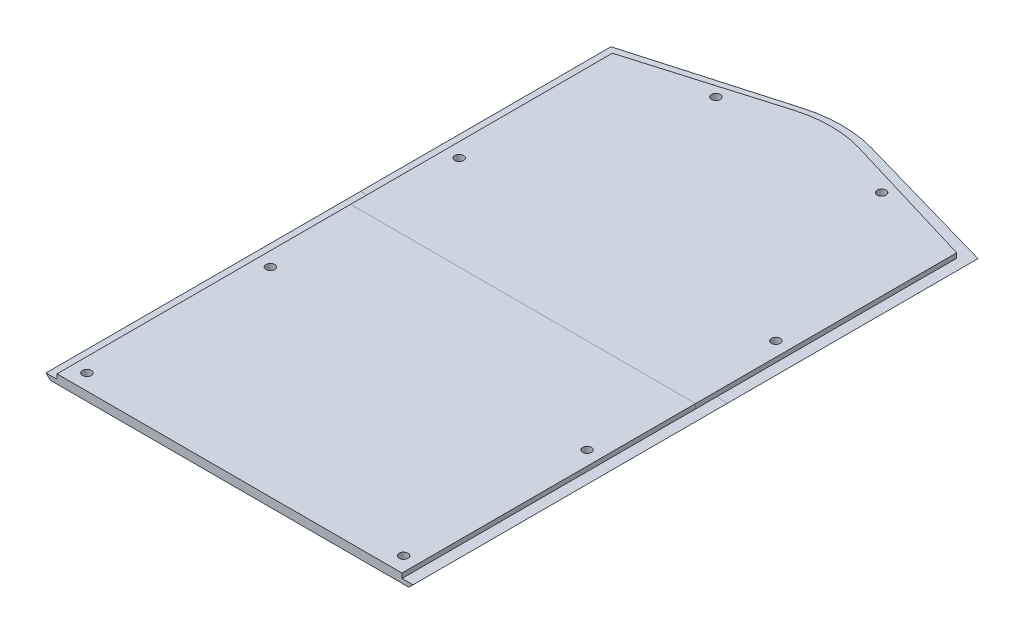
SolidWorks part; units mm, degrees
ref_plane "Front Plane" through (0, 0, 0) normal (0, 0, 1) x (1, 0, 0)
ref_plane "Top Plane" through (0, 0, 0) normal (0, 1, 0) x (1, 0, 0)
ref_plane "Right Plane" through (0, 0, 0) normal (1, 0, 0) x (0, 0, -1)
sketch "Sketch3" plane through (0, 0, 0) normal (0, -1, 0) x (1, 0, 0)
  line L0 (-82.5, -125) -> (-82.5, 140) construction
  line L1 (-15.1576, -144.8692) -> (-82.5, -125) construction
  line L2 (82.5923, -125) -> (15.2499, -144.8692) construction
  line L3 (82.5, 140) -> (82.5, -125) construction
  line L4 (-82.5, -125) -> (-82.5, 140) construction
  line L5 (-15.1576, -144.8692) -> (-82.5, -125) construction
  line L6 (82.5923, -125) -> (15.2499, -144.8692) construction
  line L7 (82.5, 140) -> (82.5, -125) construction
  line L8 (82.25, 140) -> (82.25, -124.5028)
  line L9 (82.5923, -125) -> (82.5, -125) construction
  line L10 (-15.0878, -144.6291) -> (-82.25, -124.8131)
  line L11 (-82.25, -124.8131) -> (-82.25, 140)
  line L12 (82.25, -124.5028) -> (15.1801, -144.6291)
  line L13 (82.25, 140) -> (-82.25, 140)
  line L14 (82.5216, -124.7602) -> (15.1801, -144.6291) construction
  line L15 (82.25, 140) -> (82.25, -125) construction
  arc A0 (-15.1576, -144.8692) -> (0.0462, -146.9988) centre (-0.0004, -91.995) ccw construction
  arc A1 (0.0462, -146.9988) -> (15.2499, -144.8692) centre (0.0928, -91.995) ccw construction
  arc A2 (-15.1576, -144.8692) -> (0.0462, -146.9988) centre (-0.0004, -91.995) ccw construction
  arc A3 (0.0462, -146.9988) -> (15.2499, -144.8692) centre (0.0928, -91.995) ccw construction
  arc A4 (0.0462, -146.7488) -> (15.1801, -144.6291) centre (0.0928, -91.995) ccw
  arc A5 (-15.0878, -144.6291) -> (0.0462, -146.7488) centre (-0.0004, -91.995) ccw
  dimension "D1" = 0.25
extrude "Boss-Extrude1" add sketch "Sketch3" against normal blind 2.25
sketch "Sketch4" plane through (0, 0, 0) normal (0, -1, 0) x (1, 0, 0)
  line L0 (87.5, 140) -> (-87.5, 140)
  line L11 (82.5, -125) -> (82.5923, -125)
  line L12 (82.5923, -125) -> (15.2499, -144.8692)
  line L13 (-15.1576, -144.8692) -> (-82.5, -125)
  line L14 (-82.5, -125) -> (-82.5, 140)
  line L15 (-82.5, 140) -> (-87.5, 140)
  line L16 (-87.5, 140) -> (-87.5, -129.3998)
  line L17 (-87.5, -129.3998) -> (-16.4833, -149.6903)
  line L18 (16.4833, -149.6903) -> (87.5, -129.3998)
  line L19 (87.5, -129.3998) -> (87.5, 140)
  line L20 (87.5, 140) -> (82.5, 140)
  line L21 (82.5, 140) -> (82.5, -125)
  line L27 (-87.5, 140) -> (-87.5, -129.3998)
  line L28 (-87.5, -129.3998) -> (-16.4833, -149.6903)
  line L29 (16.4833, -149.6903) -> (87.5, -129.3998)
  line L30 (87.5, -129.3998) -> (87.5, 140)
  arc A3 (0.0462, -146.9988) -> (15.2499, -144.8692) centre (0.0928, -91.995) ccw
  arc A4 (-15.1576, -144.8692) -> (0.0462, -146.9988) centre (-0.0004, -91.995) ccw
  arc A5 (-16.4833, -149.6903) -> (16.4833, -149.6903) centre (0, -91.9988) ccw
  arc A8 (-16.4833, -149.6903) -> (16.4833, -149.6903) centre (0, -91.9988) ccw
  dimension "D1" = 0
extrude "Boss-Extrude2" add sketch "Sketch4" along normal blind 2
chamfer "Chamfer1" distance 2 angle 45 5 edges at (87.5, -2, 5.3001) (51.9916, -2, -139.545) (0, -2, -151.9988) (-51.9916, -2, -139.545) (-87.5, -2, 5.3001)
sketch "Sketch5" plane through (0, -2, 0) normal (0, -1, 0) x (1, 0, 0)
  line L0 (-76.1767, 137.5155) -> (-80.1767, 135.2061) construction
  line L1 (-80.1767, 135.2061) -> (-80.1767, 130.5873) construction
  line L2 (-80.1767, 130.5873) -> (-76.1767, 128.2779) construction
  line L3 (-76.1767, 128.2779) -> (-72.1767, 130.5873) construction
  line L4 (-72.1767, 130.5873) -> (-72.1767, 135.2061) construction
  line L5 (-72.1767, 135.2061) -> (-76.1767, 137.5155) construction
  line L6 (75.5, 137.1) -> (71.5, 134.7906) construction
  line L7 (71.5, 134.7906) -> (71.5, 130.1718) construction
  line L8 (71.5, 130.1718) -> (75.5, 127.8624) construction
  line L9 (75.5, 127.8624) -> (79.5, 130.1718) construction
  line L10 (79.5, 130.1718) -> (79.5, 134.7906) construction
  line L11 (79.5, 134.7906) -> (75.5, 137.1) construction
  line L12 (75.5, 40.4) -> (79.5, 42.7094) construction
  line L13 (79.5, 42.7094) -> (79.5, 47.3282) construction
  line L14 (79.5, 47.3282) -> (75.5, 49.6376) construction
  line L15 (75.5, 49.6376) -> (71.5, 47.3282) construction
  line L16 (71.5, 47.3282) -> (71.5, 42.7094) construction
  line L17 (71.5, 42.7094) -> (75.5, 40.4) construction
  line L18 (75.5, -40.4) -> (71.5, -42.7094) construction
  line L19 (71.5, -42.7094) -> (71.5, -47.3282) construction
  line L20 (71.5, -47.3282) -> (75.5, -49.6376) construction
  line L21 (75.5, -49.6376) -> (79.5, -47.3282) construction
  line L22 (79.5, -47.3282) -> (79.5, -42.7094) construction
  line L23 (79.5, -42.7094) -> (75.5, -40.4) construction
  line L24 (-39.5, -126.8131) -> (-43.5, -129.1225) construction
  line L25 (-43.5, -129.1225) -> (-43.5, -133.7413) construction
  line L26 (-43.5, -133.7413) -> (-39.5, -136.0507) construction
  line L27 (-39.5, -136.0507) -> (-35.5, -133.7413) construction
  line L28 (-35.5, -133.7413) -> (-35.5, -129.1225) construction
  line L29 (-35.5, -129.1225) -> (-39.5, -126.8131) construction
  line L30 (39.5, -126.8131) -> (35.5, -129.1225) construction
  line L31 (35.5, -129.1225) -> (35.5, -133.7413) construction
  line L32 (35.5, -133.7413) -> (39.5, -136.0507) construction
  line L33 (39.5, -136.0507) -> (43.5, -133.7413) construction
  line L34 (43.5, -133.7413) -> (43.5, -129.1225) construction
  line L35 (43.5, -129.1225) -> (39.5, -126.8131) construction
  line L36 (-75.5, 40.4) -> (-71.5, 42.7094) construction
  line L37 (-71.5, 42.7094) -> (-71.5, 47.3282) construction
  line L38 (-71.5, 47.3282) -> (-75.5, 49.6376) construction
  line L39 (-75.5, 49.6376) -> (-79.5, 47.3282) construction
  line L40 (-79.5, 47.3282) -> (-79.5, 42.7094) construction
  line L41 (-79.5, 42.7094) -> (-75.5, 40.4) construction
  line L42 (-75.5, -40.4) -> (-79.5, -42.7094) construction
  line L43 (-79.5, -42.7094) -> (-79.5, -47.3282) construction
  line L44 (-79.5, -47.3282) -> (-75.5, -49.6376) construction
  line L45 (-75.5, -49.6376) -> (-71.5, -47.3282) construction
  line L46 (-71.5, -47.3282) -> (-71.5, -42.7094) construction
  line L47 (-71.5, -42.7094) -> (-75.5, -40.4) construction
  line L48 (-76.1767, 137.5155) -> (-80.1767, 135.2061) construction
  line L49 (-80.1767, 135.2061) -> (-80.1767, 130.5873) construction
  line L50 (-80.1767, 130.5873) -> (-76.1767, 128.2779) construction
  line L51 (-76.1767, 128.2779) -> (-72.1767, 130.5873) construction
  line L52 (-72.1767, 130.5873) -> (-72.1767, 135.2061) construction
  line L53 (-72.1767, 135.2061) -> (-76.1767, 137.5155) construction
  line L54 (75.5, 137.1) -> (71.5, 134.7906) construction
  line L55 (71.5, 134.7906) -> (71.5, 130.1718) construction
  line L56 (71.5, 130.1718) -> (75.5, 127.8624) construction
  line L57 (75.5, 127.8624) -> (79.5, 130.1718) construction
  line L58 (79.5, 130.1718) -> (79.5, 134.7906) construction
  line L59 (79.5, 134.7906) -> (75.5, 137.1) construction
  line L60 (75.5, 40.4) -> (79.5, 42.7094) construction
  line L61 (79.5, 42.7094) -> (79.5, 47.3282) construction
  line L62 (79.5, 47.3282) -> (75.5, 49.6376) construction
  line L63 (75.5, 49.6376) -> (71.5, 47.3282) construction
  line L64 (71.5, 47.3282) -> (71.5, 42.7094) construction
  line L65 (71.5, 42.7094) -> (75.5, 40.4) construction
  line L66 (75.5, -40.4) -> (71.5, -42.7094) construction
  line L67 (71.5, -42.7094) -> (71.5, -47.3282) construction
  line L68 (71.5, -47.3282) -> (75.5, -49.6376) construction
  line L69 (75.5, -49.6376) -> (79.5, -47.3282) construction
  line L70 (79.5, -47.3282) -> (79.5, -42.7094) construction
  line L71 (79.5, -42.7094) -> (75.5, -40.4) construction
  line L72 (-39.5, -126.8131) -> (-43.5, -129.1225) construction
  line L73 (-43.5, -129.1225) -> (-43.5, -133.7413) construction
  line L74 (-43.5, -133.7413) -> (-39.5, -136.0507) construction
  line L75 (-39.5, -136.0507) -> (-35.5, -133.7413) construction
  line L76 (-35.5, -133.7413) -> (-35.5, -129.1225) construction
  line L77 (-35.5, -129.1225) -> (-39.5, -126.8131) construction
  line L78 (39.5, -126.8131) -> (35.5, -129.1225) construction
  line L79 (35.5, -129.1225) -> (35.5, -133.7413) construction
  line L80 (35.5, -133.7413) -> (39.5, -136.0507) construction
  line L81 (39.5, -136.0507) -> (43.5, -133.7413) construction
  line L82 (43.5, -133.7413) -> (43.5, -129.1225) construction
  line L83 (43.5, -129.1225) -> (39.5, -126.8131) construction
  line L84 (-75.5, 40.4) -> (-71.5, 42.7094) construction
  line L85 (-71.5, 42.7094) -> (-71.5, 47.3282) construction
  line L86 (-71.5, 47.3282) -> (-75.5, 49.6376) construction
  line L87 (-75.5, 49.6376) -> (-79.5, 47.3282) construction
  line L88 (-79.5, 47.3282) -> (-79.5, 42.7094) construction
  line L89 (-79.5, 42.7094) -> (-75.5, 40.4) construction
  line L90 (-75.5, -40.4) -> (-79.5, -42.7094) construction
  line L91 (-79.5, -42.7094) -> (-79.5, -47.3282) construction
  line L92 (-79.5, -47.3282) -> (-75.5, -49.6376) construction
  line L93 (-75.5, -49.6376) -> (-71.5, -47.3282) construction
  line L94 (-71.5, -47.3282) -> (-71.5, -42.7094) construction
  line L95 (-71.5, -42.7094) -> (-75.5, -40.4) construction
  line L96 (0, -33) -> (0, 33) construction
  circle A0 centre (39.5, -131.4319) radius 2.1
  circle A1 centre (75.5, -45.0188) radius 2.1
  circle A2 centre (75.5, 45.0188) radius 2.1
  circle A3 centre (75.5, 132.4812) radius 2.1
  circle A4 centre (-75.5, 132.4812) radius 2.1
  circle A5 centre (-75.5, 45.0188) radius 2.1
  circle A6 centre (-75.5, -45.0188) radius 2.1
  circle A7 centre (-39.5, -131.4319) radius 2.1
  point P6 (71.5, -45.0188)
  point P8 (35.5, -131.4319)
  point P14 (71.5, 45.0188)
  point P23 (0, 0)
  point P26 (71.5, 132.4812)
  dimension "D1" = 4.2
extrude "Cut-Extrude1" cut sketch "Sketch5" against normal up to next
sketch "Sketch6" plane through (0, 0, 0) normal (1, 0, 0) x (0, 0, -1)
  line L0 (10, -2) -> (10, 0)
  line L1 (127.8912, -2) -> (-140, -2) construction
  line L2 (10, 0) -> (0, 0)
  line L3 (0, 0) -> (0, 2.25)
  line L4 (124.5028, 2.25) -> (-140, 2.25) construction
  line L5 (129.3998, 0) -> (-140, 0) construction
  dimension "D1" = 10
split "Split1" trim tools "Sketch6" bodies to split 103 resulting bodies 104 105
sketch "Sketch7" plane through (0, 0, 0) normal (0, -1, 0) x (1, 0, 0)
  line L0 (82.25, -10) -> (82.25, 0) construction
  line L1 (0, -2.3375) -> (0, 2.3375) construction
  circle A0 centre (72.25, -5) radius 2.5
  circle A1 centre (-72.25, -5) radius 2.5
  point P4 (0, 0)
  point P5 (82.25, -5)
  dimension "D1" = 5
  dimension "D2" = 10
extrude "Boss-Extrude3" add sketch "Sketch7" along normal blind 2
chamfer "Chamfer2" distance 0.25 angle 45 1 edges at (72.25, -2, -7.5)
sketch "Sketch9" plane through (0, 0, 0) normal (0, 1, 0) x (1, 0, 0)
  line L1 (72.25, 0) -> (72.25, 10) construction
  line L2 (-87.5, 10) -> (87.5, 10) construction
  line L3 (-82.25, 0) -> (82.25, 0) construction
  line L4 (0, -2.3375) -> (0, 2.3375) construction
  line L5 (82.25, 124.5028) -> (82.25, 0) construction
  circle A0 centre (72.25, 5) radius 2.5
  circle A1 centre (-72.25, 5) radius 2.5
  point P4 (0, 0)
  point P10 (72.25, 5)
  point P12 (0, 0)
  point P13 (0, 0)
  dimension "D1" = 5
  dimension "D2" = 10
extrude "Cut-Extrude2" cut sketch "Sketch9" against normal blind 2
